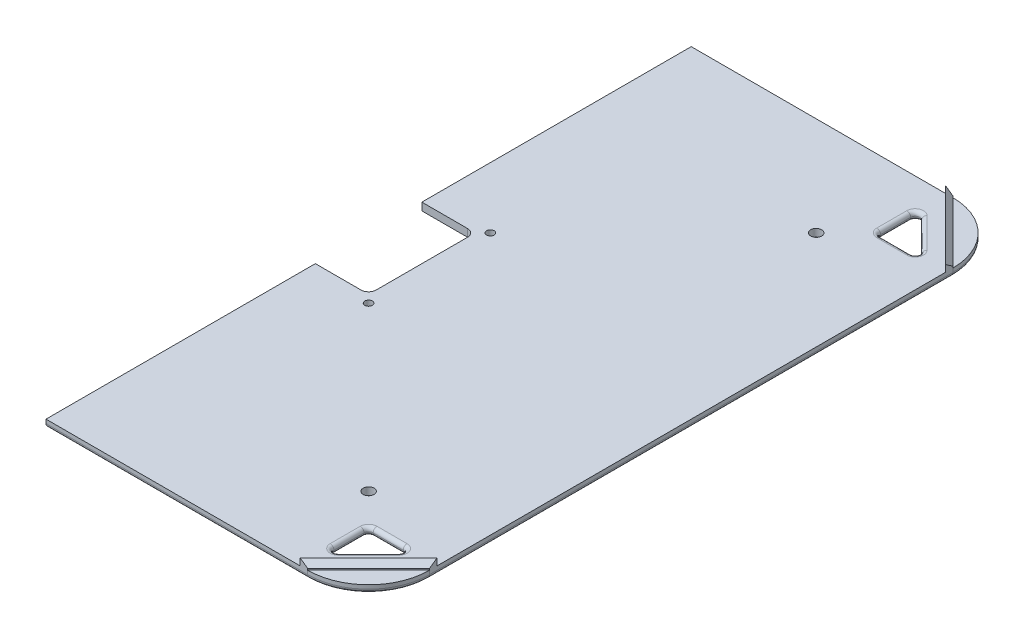
SolidWorks part; units mm, degrees
ref_plane "Front Plane" through (0, 0, 0) normal (0, 0, 1) x (1, 0, 0)
ref_plane "Top Plane" through (0, 0, 0) normal (0, 1, 0) x (1, 0, 0)
ref_plane "Right Plane" through (0, 0, 0) normal (1, 0, 0) x (0, 0, -1)
sketch "Sketch1" plane through (0, 0, 0) normal (0, 1, 0) x (1, 0, 0)
  line L0 (0, -134.62) -> (0, 134.62)
  line L1 (-134.62, -134.62) -> (134.62, -134.62)
  line L2 (-134.62, -134.62) -> (-134.62, 134.62)
  line L3 (-134.62, 134.62) -> (134.62, 134.62)
  line L4 (134.62, -134.62) -> (134.62, 134.62)
  line L5 (-134.62, -134.62) -> (134.62, 134.62) construction
  line L6 (-134.62, 134.62) -> (134.62, -134.62) construction
  point P0 (0, 0)
  point P9 (0, 0)
  dimension "D1" = 269.24
extrude "Boss-Extrude1" add sketch "Sketch1" along normal blind 3.175 contours L1 L4 L3 L0 region at (67.31, 0, 0)
sketch "Sketch2" plane through (0, 3.175, 0) normal (0, 1, 0) x (1, 0, 0)
  line L0 (109.22, 134.62) -> (134.62, 109.22)
  line L1 (109.22, 134.62) -> (106.045, 134.62)
  line L2 (106.045, 134.62) -> (134.62, 106.045)
  line L3 (134.62, 106.045) -> (134.62, 109.22)
  line L4 (0, -134.62) -> (134.62, -134.62)
  line L5 (134.62, -134.62) -> (134.62, 134.62)
  line L6 (134.62, 134.62) -> (0, 134.62)
  line L7 (0, 134.62) -> (0, -134.62)
  line L8 (0, -134.62) -> (134.62, -134.62)
  line L9 (134.62, -134.62) -> (134.62, 134.62)
  line L10 (134.62, 134.62) -> (0, 134.62)
  line L11 (0, 134.62) -> (0, -134.62)
  line L12 (109.22, -134.62) -> (134.62, -109.22)
  line L13 (134.62, -109.22) -> (134.62, -106.045)
  line L14 (134.62, -106.045) -> (106.045, -134.62)
  line L15 (106.045, -134.62) -> (109.22, -134.62)
  line L16 (120.3325, -120.3325) -> (115.3934, -115.3934)
  line L17 (120.3325, 120.3325) -> (115.3934, 115.3934)
  line L18 (105.8684, -124.9184) -> (124.9184, -105.8684)
  line L19 (124.9184, -105.8684) -> (105.8684, -105.8684)
  line L20 (105.8684, -105.8684) -> (105.8684, -124.9184)
  line L21 (124.9184, 105.8684) -> (105.8684, 124.9184)
  line L22 (105.8684, 124.9184) -> (105.8684, 105.8684)
  line L23 (105.8684, 105.8684) -> (124.9184, 105.8684)
  line L24 (120.3325, -120.3325) -> (93.3917, -93.3917)
  line L25 (120.3325, 120.3325) -> (93.3917, 93.3917)
  circle A0 centre (93.3917, -93.3917) radius 2.286
  circle A1 centre (93.3917, 93.3917) radius 2.286
  point P10 (120.3325, -120.3325)
  point P13 (120.3325, 120.3325)
  point P21 (115.3934, -115.3934)
  point P25 (115.3934, 115.3934)
  line M24 (134.62, -134.62) -> (134.62, 134.62)
  line M25 (134.62, 134.62) -> (0, 134.62)
  dimension "D17" = 4.572
  dimension "D2" = 3.175
  dimension "D3" = 25.4
  dimension "D4" = 3.175
  dimension "D5" = 25.4
  dimension "D6" = 3.175
  dimension "D7" = 3.175
  dimension "D8" = 25.4
  dimension "D9" = 6.985
  dimension "D10" = 90
  dimension "D11" = 6.985
  dimension "D12" = 90
  dimension "D13" = 19.05
  dimension "D14" = 19.05
  dimension "D15" = 38.1
  dimension "D16" = 90
  dimension "D18" = 90
  dimension "D1" = 0
extrude "Boss-Extrude2" add sketch "Sketch2" along normal blind 3.175 contours L2 L0 M25 M24 | L9 L14 L8 L12 region at (121.1107, 3.175, -121.1107) region at (121.1107, 3.175, 121.1107)
extrude "Cut-Extrude1" cut sketch "Sketch2<3>" against normal up to next contours L22 L23 L21 | A1 | L20 L18 L19 | A0
sketch "Sketch2<3>" plane through (0, 3.175, 0) normal (0, 1, 0) x (1, 0, 0) same geometry as "Sketch2"
chamfer "Chamfer1" distance 2.54 2 edges at (121.92, 6.35, 121.92) (121.92, 6.35, -121.92)
fillet "Fillet1" radius 1.905 6 edges at (105.8684, 1.5875, -105.8684) (124.9184, 1.5875, -105.8684) (105.8684, 1.5875, -124.9184) (105.8684, 1.5875, 105.8684) (105.8684, 1.5875, 124.9184) (124.9184, 1.5875, 105.8684)
fillet "Fillet2" radius 1.5875 24 edges at (107.0443, 3.175, 122.0793) (105.8684, 3.175, 114.0463) (106.4263, 3.175, 106.4263) (114.0463, 3.175, 105.8684) (122.0793, 3.175, 107.0443) (122.0793, 0, 107.0443) (114.0463, 0, 105.8684) (106.4263, 0, 106.4263) (105.8684, 0, 114.0463) (107.0443, 0, 122.0793) (122.0793, 3.175, -107.0443) (114.0463, 3.175, -105.8684) (106.4263, 3.175, -106.4263) (105.8684, 3.175, -114.0463) (107.0443, 3.175, -122.0793) (107.0443, 0, -122.0793) (105.8684, 0, -114.0463) (106.4263, 0, -106.4263) (114.0463, 0, -105.8684) (122.0793, 0, -107.0443) (115.3934, 3.175, 115.3934) (115.3934, 0, 115.3934) (115.3934, 3.175, -115.3934) (115.3934, 0, -115.3934)
fillet "Fillet3" radius 25.4 2 edges at (134.62, 1.5875, -134.62) (134.62, 1.5875, 134.62)
fillet "Fillet4" radius 1.5875 5 edges at (54.61, 0, 134.62) (127.1805, 0, 127.1805) (54.61, 0, -134.62) (127.1805, 0, -127.1805) (134.62, 0, 0)
sketch "Sketch3" plane through (0, 0, 0) normal (0, -1, 0) x (1, 0, 0)
  line L1 (0, -28.575) -> (31.75, -28.575)
  line L2 (0, -28.575) -> (0, 28.575)
  line L3 (0, 28.575) -> (31.75, 28.575)
  line L4 (109.22, 133.0325) -> (0, 133.0325)
  line L5 (0, 133.0325) -> (0, -133.0325)
  line L6 (0, -133.0325) -> (109.22, -133.0325)
  line L7 (133.0325, -109.22) -> (133.0325, 109.22)
  line L8 (109.22, 133.0325) -> (0, 133.0325)
  line L9 (0, 133.0325) -> (0, -133.0325)
  line L10 (0, -133.0325) -> (109.22, -133.0325)
  line L11 (133.0325, -109.22) -> (133.0325, 109.22)
  line L12 (31.75, -28.575) -> (31.75, 28.575)
  line L13 (0, 110.8075) -> (31.75, 110.8075)
  line L14 (0, 110.8075) -> (0, 53.6575)
  line L15 (0, 53.6575) -> (31.75, 53.6575)
  line L16 (31.75, 110.8075) -> (31.75, 53.6575)
  line L17 (0, -53.6575) -> (31.75, -53.6575)
  line L18 (0, -53.6575) -> (0, -110.8075)
  line L19 (0, -110.8075) -> (31.75, -110.8075)
  line L20 (31.75, -53.6575) -> (31.75, -110.8075)
  arc A2 (133.0325, 109.22) -> (109.22, 133.0325) centre (109.22, 109.22) ccw
  arc A3 (109.22, -133.0325) -> (133.0325, -109.22) centre (109.22, -109.22) ccw
  arc A4 (133.0325, 109.22) -> (109.22, 133.0325) centre (109.22, 109.22) ccw
  arc A5 (109.22, -133.0325) -> (133.0325, -109.22) centre (109.22, -109.22) ccw
  point P20 (0, 82.2325)
  point P21 (0, 0)
  point P22 (0, -82.2325)
  point P23 (0, 0)
  point P25 (0, 0)
  point P26 (0, 0)
  dimension "D2" = 57.15
  dimension "D3" = 31.75
  dimension "D4" = 50.8
  dimension "D5" = 50.8
  dimension "D1" = 0
extrude "Boss-Extrude3" add sketch "Sketch3" along normal blind 3.175 contours L16 L13 L9 L15 | L20 L17 L9 L19 region at (15.875, 0, -82.2325) region at (15.875, 0, 82.2325)
sketch "Sketch4" plane through (0, 0, 0) normal (-1, 0, 0) x (0, 0, 1)
  line L0 (110.8075, 0) -> (110.8075, 3.175)
  line L1 (110.8075, 3.175) -> (53.6575, 3.175)
  line L2 (53.6575, 3.175) -> (53.6575, 0)
  line L3 (-53.6575, 0) -> (-53.6575, 3.175)
  line L4 (-53.6575, 3.175) -> (53.6575, 3.175)
  line L5 (53.6575, 3.175) -> (53.6575, 0)
  line L6 (-53.6575, 0) -> (-53.6575, 3.175)
  line L7 (-53.6575, 3.175) -> (-110.8075, 3.175)
  line L8 (-110.8075, 3.175) -> (-110.8075, 0)
  line L9 (-53.6575, 3.175) -> (-110.8075, 3.175)
  line L10 (-53.6575, 3.175) -> (53.6575, 3.175)
  line L12 (-107.6325, 1.5875) -> (-56.8325, 1.5875)
  line L13 (-107.6325, 1.5875) -> (-107.6325, -1.5875)
  line L14 (-107.6325, -1.5875) -> (-56.8325, -1.5875)
  line L15 (-56.8325, 1.5875) -> (-56.8325, -1.5875)
  line L16 (110.8075, 0) -> (133.0325, 0)
  line L17 (134.62, 1.5875) -> (134.62, 3.175)
  line L18 (134.62, 3.175) -> (-134.62, 3.175)
  line L19 (-134.62, 3.175) -> (-134.62, 1.5875)
  line L20 (-133.0325, 0) -> (-110.8075, 0)
  line L21 (-110.8075, 0) -> (-110.8075, -3.175)
  line L22 (-110.8075, -3.175) -> (-53.6575, -3.175)
  line L23 (-53.6575, -3.175) -> (-53.6575, 0)
  line L24 (-53.6575, 0) -> (53.6575, 0)
  line L29 (53.6575, 0) -> (53.6575, -3.175)
  line L30 (53.6575, -3.175) -> (110.8075, -3.175)
  line L31 (110.8075, -3.175) -> (110.8075, 0)
  line L34 (110.8075, 3.175) -> (53.6575, 3.175)
  line L37 (-110.8075, 0) -> (-110.8075, -3.175)
  line L38 (-110.8075, -3.175) -> (-53.6575, -3.175)
  line L39 (-53.6575, -3.175) -> (-53.6575, 0)
  line L45 (53.6575, 0) -> (53.6575, -3.175)
  line L46 (53.6575, -3.175) -> (110.8075, -3.175)
  line L47 (110.8075, -3.175) -> (110.8075, 0)
  line L48 (-107.6325, 1.5875) -> (-56.8325, -1.5875) construction
  line L49 (-107.6325, -1.5875) -> (-56.8325, 1.5875) construction
  line L50 (-25.4, 1.5875) -> (25.4, 1.5875)
  line L51 (-25.4, 1.5875) -> (-25.4, -1.5875)
  line L52 (-25.4, -1.5875) -> (25.4, -1.5875)
  line L53 (25.4, 1.5875) -> (25.4, -1.5875)
  line L54 (-25.4, 1.5875) -> (25.4, -1.5875) construction
  line L55 (-25.4, -1.5875) -> (25.4, 1.5875) construction
  line L56 (56.8325, 1.5875) -> (107.6325, 1.5875)
  line L57 (56.8325, 1.5875) -> (56.8325, -1.5875)
  line L58 (56.8325, -1.5875) -> (107.6325, -1.5875)
  line L59 (107.6325, 1.5875) -> (107.6325, -1.5875)
  line L60 (56.8325, 1.5875) -> (107.6325, -1.5875) construction
  line L61 (56.8325, -1.5875) -> (107.6325, 1.5875) construction
  arc A2 (133.0325, 0) -> (134.62, 1.5875) centre (133.0325, 1.5875) ccw
  arc A3 (-134.62, 1.5875) -> (-133.0325, 0) centre (-133.0325, 1.5875) ccw
  point P16 (82.2325, 3.175)
  point P18 (0, 3.175)
  point P20 (-82.2325, 3.175)
  point P22 (-82.2325, 0)
  point P32 (0, 0)
  point P40 (82.2325, 0)
  point P45 (0, 0)
  point P46 (0, 0)
  point P47 (0, 0)
  point P48 (0, 0)
  point P49 (0, 0)
  point P50 (0, 0)
  dimension "D2" = 50.8
  dimension "D3" = 3.175
  dimension "D1" = 0
extrude "Cut-Extrude2" cut sketch "Sketch4" against normal blind 19.05 contours L59 L56 L57 L58 | L15 L12 L13 L14 region at (0, 0, -82.2325) region at (0, 0, 82.2325)
fillet "Fillet5" radius 12.7 4 edges at (31.75, -1.5875, 110.8075) (31.75, -1.5875, 53.6575) (31.75, -1.5875, -53.6575) (31.75, -1.5875, -110.8075)
fillet "Fillet6" radius 3.175 10 edges at (9.525, -3.175, -110.8075) (28.0303, -3.175, -107.0878) (31.75, -3.175, -82.2325) (28.0303, -3.175, -57.3772) (9.525, -3.175, 53.6575) (28.0303, -3.175, 57.3772) (31.75, -3.175, 82.2325) (28.0303, -3.175, 107.0878) (9.525, -3.175, -53.6575) (9.525, -3.175, 110.8075)
sketch "Sketch5" plane through (0, 0, 0) normal (0, -1, 0) x (1, 0, 0)
  line L1 (-22.225, 22.225) -> (22.225, 22.225)
  line L2 (-22.225, 22.225) -> (-22.225, -22.225)
  line L3 (-22.225, -22.225) -> (22.225, -22.225)
  line L4 (22.225, 22.225) -> (22.225, -22.225)
  line L5 (-22.225, 22.225) -> (22.225, -22.225) construction
  line L6 (-22.225, -22.225) -> (22.225, 22.225) construction
  line L7 (-25.4, 25.4) -> (25.4, 25.4)
  line L8 (-25.4, 25.4) -> (-25.4, -25.4)
  line L9 (-25.4, -25.4) -> (25.4, -25.4)
  line L10 (25.4, 25.4) -> (25.4, -25.4)
  line L11 (-25.4, 25.4) -> (25.4, -25.4) construction
  line L12 (0, 53.6575) -> (0, -53.6575)
  line L13 (0, -53.6575) -> (19.05, -53.6575)
  line L14 (31.75, -66.3575) -> (31.75, -98.1075)
  line L15 (19.05, -110.8075) -> (0, -110.8075)
  line L16 (0, -110.8075) -> (0, -133.0325)
  line L17 (0, -133.0325) -> (109.22, -133.0325)
  line L18 (133.0325, -109.22) -> (133.0325, 109.22)
  line L19 (109.22, 133.0325) -> (0, 133.0325)
  line L20 (0, 133.0325) -> (0, 110.8075)
  line L21 (0, 110.8075) -> (19.05, 110.8075)
  line L22 (31.75, 98.1075) -> (31.75, 66.3575)
  line L23 (19.05, 53.6575) -> (0, 53.6575)
  line L24 (0, 53.6575) -> (0, -53.6575)
  line L25 (0, -53.6575) -> (19.05, -53.6575)
  line L26 (31.75, -66.3575) -> (31.75, -98.1075)
  line L27 (19.05, -110.8075) -> (0, -110.8075)
  line L28 (0, -110.8075) -> (0, -133.0325)
  line L29 (0, -133.0325) -> (109.22, -133.0325)
  line L30 (133.0325, -109.22) -> (133.0325, 109.22)
  line L31 (109.22, 133.0325) -> (0, 133.0325)
  line L32 (0, 133.0325) -> (0, 110.8075)
  line L33 (0, 110.8075) -> (19.05, 110.8075)
  line L34 (31.75, 98.1075) -> (31.75, 66.3575)
  line L35 (19.05, 53.6575) -> (0, 53.6575)
  line L36 (-25.4, -25.4) -> (25.4, 25.4) construction
  circle A0 centre (25.4, 25.4) radius 1.5875
  circle A1 centre (25.4, -25.4) radius 1.5875
  arc A6 (31.75, -66.3575) -> (19.05, -53.6575) centre (19.05, -66.3575) ccw
  arc A7 (19.05, -110.8075) -> (31.75, -98.1075) centre (19.05, -98.1075) ccw
  arc A8 (109.22, -133.0325) -> (133.0325, -109.22) centre (109.22, -109.22) ccw
  arc A9 (133.0325, 109.22) -> (109.22, 133.0325) centre (109.22, 109.22) ccw
  arc A10 (31.75, 98.1075) -> (19.05, 110.8075) centre (19.05, 98.1075) ccw
  arc A11 (19.05, 53.6575) -> (31.75, 66.3575) centre (19.05, 66.3575) ccw
  arc A12 (31.75, -66.3575) -> (19.05, -53.6575) centre (19.05, -66.3575) ccw
  arc A13 (19.05, -110.8075) -> (31.75, -98.1075) centre (19.05, -98.1075) ccw
  arc A14 (109.22, -133.0325) -> (133.0325, -109.22) centre (109.22, -109.22) ccw
  arc A15 (133.0325, 109.22) -> (109.22, 133.0325) centre (109.22, 109.22) ccw
  arc A16 (31.75, 98.1075) -> (19.05, 110.8075) centre (19.05, 98.1075) ccw
  arc A17 (19.05, 53.6575) -> (31.75, 66.3575) centre (19.05, 66.3575) ccw
  point P4 (0, 0)
  point P21 (0, 0)
  line M41 (0, 53.6575) -> (0, -53.6575)
  dimension "D4" = 3.175
  dimension "D2" = 44.45
  dimension "D3" = 50.8
  dimension "D1" = 0
extrude "Cut-Extrude3" cut sketch "Sketch5" against normal up to next contours L4 L1 L3 M41 | A0 | A1 region at (11.1125, 0, 0)
fillet "Fillet7" radius 3.175 2 edges at (22.225, 1.5875, -22.225) (22.225, 1.5875, 22.225)
